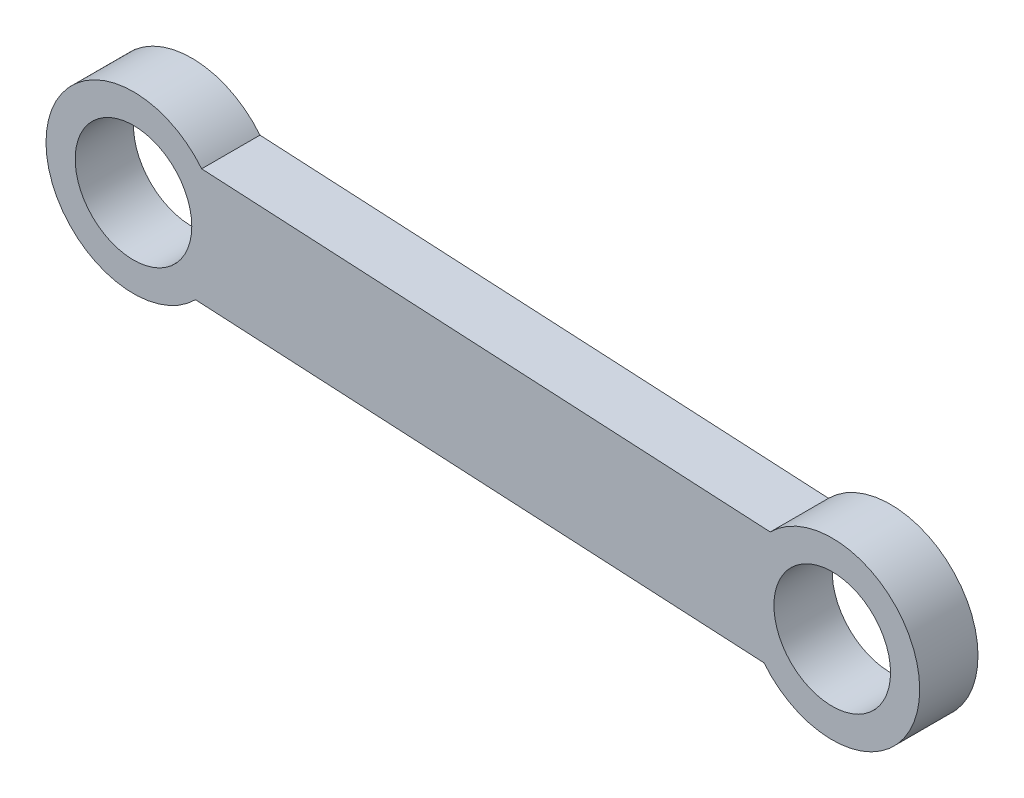
SolidWorks part; units mm, degrees
ref_plane "Front Plane" through (0, 0, 0) normal (0, 0, 1) x (1, 0, 0)
ref_plane "Top Plane" through (0, 0, 0) normal (0, 1, 0) x (1, 0, 0)
ref_plane "Right Plane" through (0, 0, 0) normal (1, 0, 0) x (0, 0, -1)
sketch "Sketch1" plane through (0, 0, 0) normal (0, 0, 1) x (0.4312, 0.9023, 0)
  line L0 (-23.2742, 28.2643) -> (-18.6548, 30.1777) construction
  line L1 (-18.6548, 30.1777) -> (-27.8936, 26.3509) construction
  line L2 (-18.6548, 30.1777) -> (-41.6158, 85.6105)
  line L3 (-27.8936, 26.3509) -> (-50.8546, 81.7837)
  line L4 (-41.6158, 85.6105) -> (-50.8546, 81.7837) construction
  arc A1 (-27.8936, 26.3509) -> (-18.6548, 30.1777) centre (-23.2742, 28.2643) ccw
  arc A2 (-50.8546, 81.7837) -> (-41.6158, 85.6105) centre (-46.2352, 83.6971) cw
  circle A4 centre (-46.2352, 83.6971) radius 5
  circle A5 centre (-46.2352, 83.6971) radius 7.5
  circle A6 centre (-23.2742, 28.2643) radius 5
  circle A7 centre (-23.2742, 28.2643) radius 7.5
  dimension "D1" = 10
  dimension "D3" = 5
  dimension "D6" = 5
  dimension "D2" = 60
extrude "Boss-Extrude1" add sketch "Sketch1" along normal blind 5 contours A7 L2 A5 L3 | L3 A5 L2 A4 | L2 A5 L3 A2 | L3 A7 L2 A1 | L2 A7 L3 A6 region at (-40.7859, -8.5335, 0) region at (-38.052, -3.4623, 0) region at (-65.495, -7.2201, 0) region at (-90.2042, -5.9068, 0) region at (-92.3851, -0.5743, 0)
move or copy body "Body-Move/Copy1" [suppressed] bodies to move or copy 101
